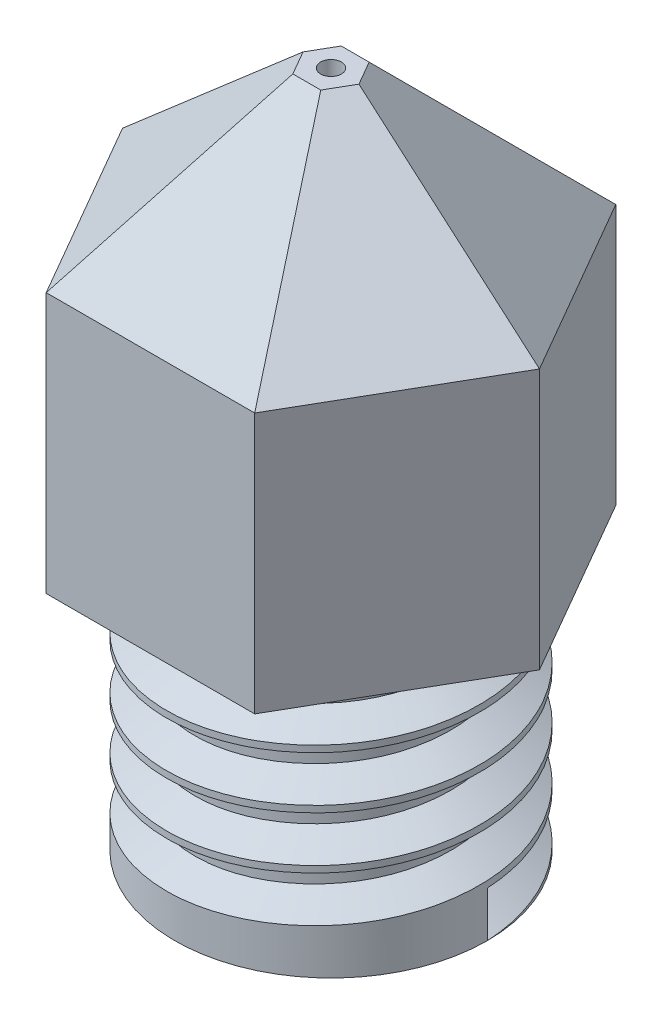
SolidWorks part; units mm, degrees
material "Brass"
ref_plane "Front Plane" through (0, 0, 0) normal (0, 0, 1) x (1, 0, 0)
ref_plane "Top Plane" through (0, 0, 0) normal (0, 1, 0) x (1, 0, 0)
ref_plane "Right Plane" through (0, 0, 0) normal (1, 0, 0) x (0, 0, -1)
sketch "Sketch1" plane through (0, 0, 0) normal (0, 1, 0) x (1, 0, 0)
  line L1 (4, 0) -> (2, 3.4641)
  line L2 (2, 3.4641) -> (-2, 3.4641)
  line L3 (-2, 3.4641) -> (-4, 0)
  line L4 (-4, 0) -> (-2, -3.4641)
  line L5 (-2, -3.4641) -> (2, -3.4641)
  line L6 (2, -3.4641) -> (4, 0)
  circle A0 centre (0, 0) radius 3.4641 construction
  dimension "D1" = 4
extrude "Boss-Extrude1" add sketch "Sketch1" along normal blind 8
chamfer "Chamfer1" distance 3 angle 45 6 edges at (0, 8, 3.4641) (-3, 8, 1.7321) (-3, 8, -1.7321) (0, 8, -3.4641) (3, 8, -1.7321) (3, 8, 1.7321)
sketch "Sketch2" plane through (0, 0, 0) normal (0, -1, 0) x (1, 0, 0)
  circle A0 centre (0, 0) radius 3
  dimension "D1" = 6
extrude "Boss-Extrude2" add sketch "Sketch2" along normal blind 5
sketch "Sketch3" plane through (0, -5, 0) normal (0, -1, 0) x (1, 0, 0)
  circle A0 centre (0, 0) radius 1.5
  dimension "D1" = 3
extrude "Cut-Extrude1" cut sketch "Sketch3" against normal blind 7
thread "Thread1" pitch 1 method cut profile "Thread Profile1" start angle 0, offset 0, length 8, pitch 1, diameter 6
ref_plane "Plane1" through (3, -5, 0) normal (0, 0, 1) x (1, 0, 0)
sketch "Thread Profile1" plane through (3, -5, 0) normal (0, 0, 1) x (1, 0, 0)
  line L0 (0, 0) -> (0, 1) construction
  line L11 (0, 0) -> (0, 0.875)
  line L12 (0, 0.875) -> (-0.5413, 0.5625)
  line L13 (-0.5413, 0.5625) -> (-0.5413, 0.3125)
  line L15 (-0.5413, 0.3125) -> (0, 0)
  line L17 (-0.5413, 0.4375) -> (0, 0.4375) construction
  point P2 (0, 0)
  dimension "Pitch" = 1
  dimension "Profile_Angle" = 60
  dimension "Profile_Land" = 0.25
  dimension "Profile_Height" = 0.5413
sketch "Sketch8" plane through (0, 8, 0) normal (0, 1, 0) x (1, 0, 0)
  circle A0 centre (0, 0) radius 0.2
  dimension "D1" = 0.4
extrude "Cut-Extrude2" cut sketch "Sketch8" against normal blind 10
